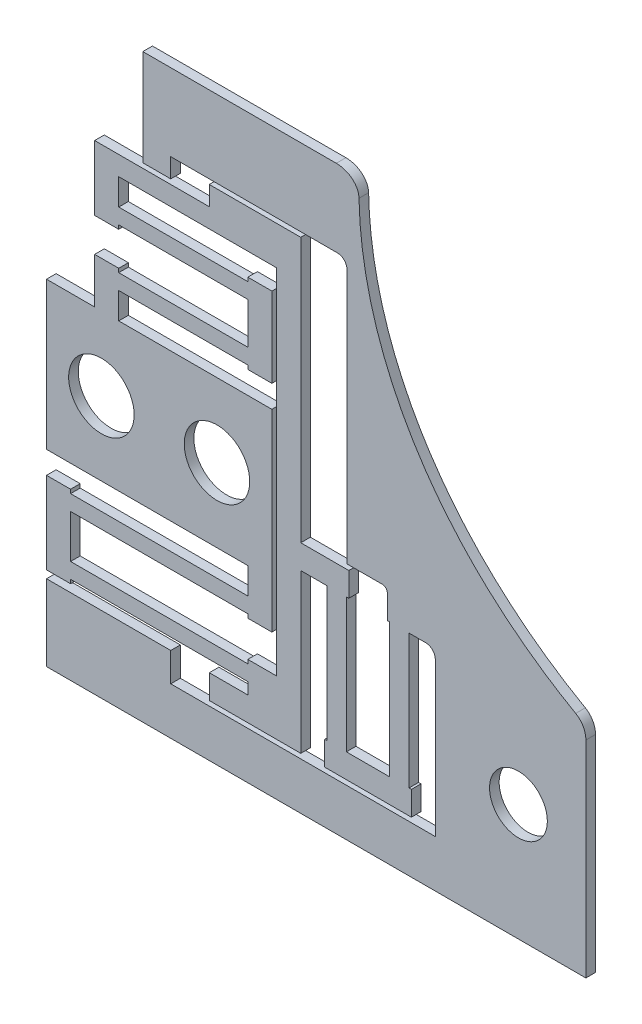
SolidWorks part; units mm, degrees
ref_plane "Front Plane" through (0, 0, 0) normal (0, 0, 1) x (1, 0, 0)
ref_plane "Top Plane" through (0, 0, 0) normal (0, 1, 0) x (1, 0, 0)
ref_plane "Right Plane" through (0, 0, 0) normal (1, 0, 0) x (0, 0, -1)
sketch "Sketch3" plane through (0, 0, 0) normal (0, 0, 1) x (1, 0, 0)
  line L80 (3.75, 14.9667) -> (11.7, 14.9667)
  line L81 (11.7, 14.9667) -> (11.7, 4.95)
  line L82 (0, 14.9667) -> (0, 7.3167)
  line L83 (0, 7.3167) -> (10.45, 7.3167)
  line L84 (1.25, 5.15) -> (1.25, 2.9)
  line L85 (1.25, 2.9) -> (10.45, 2.9)
  line L86 (10.45, 7.3167) -> (10.45, 5.95)
  line L87 (0, 6.15) -> (0, 1.9)
  line L88 (11.95, 21.45) -> (11.95, 3.1)
  line L89 (3.75, 16.3333) -> (10.45, 16.3333)
  line L90 (10.45, 17.1333) -> (10.45, 19.2833)
  line L91 (2.5, 19.0833) -> (2.5, 22.45)
  line L92 (3.75, 14.9667) -> (3.75, 16.3333)
  line L93 (11.7, 16.1333) -> (11.7, 20.2833)
  line L94 (3.75, 20.0833) -> (3.75, 21.45)
  line L95 (3.75, 21.45) -> (11.95, 21.45)
  line L96 (2.5, 22.45) -> (8.45, 22.45)
  line L97 (10.45, 16.3333) -> (10.45, 16.1333)
  line L98 (10.45, 16.1333) -> (11.7, 16.1333)
  line L99 (10.45, 17.1333) -> (3.75, 17.1333)
  line L100 (3.75, 17.1333) -> (3.75, 17.3333)
  line L101 (3.75, 17.3333) -> (2.5, 17.3333)
  line L102 (10.45, 19.2833) -> (3.75, 19.2833)
  line L103 (3.75, 19.2833) -> (3.75, 19.0833)
  line L104 (3.75, 19.0833) -> (2.5, 19.0833)
  line L105 (3.75, 20.0833) -> (10.45, 20.0833)
  line L106 (10.45, 20.0833) -> (10.45, 20.2833)
  line L107 (10.45, 20.2833) -> (11.7, 20.2833)
  line L108 (10.45, 5.95) -> (1.25, 5.95)
  line L109 (1.25, 5.95) -> (1.25, 6.15)
  line L110 (1.25, 6.15) -> (0, 6.15)
  line L111 (11.7, 4.95) -> (10.45, 4.95)
  line L112 (10.45, 4.95) -> (10.45, 5.15)
  line L113 (10.45, 5.15) -> (1.25, 5.15)
  line L114 (10.45, 2.9) -> (10.45, 3.1)
  line L115 (10.45, 3.1) -> (11.95, 3.1)
  line L116 (0, 1.9) -> (1.25, 1.9)
  line L117 (1.25, 1.9) -> (1.25, 2.1)
  line L118 (1.25, 2.1) -> (10.45, 2.1)
  line L119 (10.45, 2.1) -> (10.45, 1.5)
  line L120 (10.45, 1.5) -> (8.45, 1.5)
  line L121 (8.45, 1.5) -> (8.45, 0.25)
  line L122 (8.45, 0.25) -> (13.2, 0.25)
  line L123 (17.8167, 1.5) -> (15.5667, 1.5)
  line L124 (15.5667, 1.5) -> (15.5667, 8.4667)
  line L125 (15.5667, 8.4667) -> (15.6917, 8.4667)
  line L126 (17.8167, 8.4667) -> (17.8167, 1.5)
  line L127 (14.5667, 1.5) -> (14.4417, 1.5)
  line L128 (14.5667, 1.5) -> (14.5667, 8.4667)
  line L129 (14.5667, 8.4667) -> (13.2, 8.4667)
  line L130 (13.2, 9.7167) -> (15.6917, 9.7167)
  line L131 (19.6833, 8.4667) -> (18.8167, 8.4667)
  line L132 (18.8167, 8.4667) -> (18.8167, 1.5)
  line L133 (20.1833, 0) -> (20.1833, 7.9667)
  line L134 (20.1833, 0) -> (6.45, 0)
  line L135 (6.45, 0) -> (6.45, 1.5)
  line L136 (6.45, 1.5) -> (-4, 1.5)
  line L137 (-4, -2.45) -> (28, -2.45)
  line L138 (28, 27.7) -> (5, 27.7)
  line L139 (13.2, 0.25) -> (13.2, 8.4667)
  line L140 (6.45, 22.7) -> (5, 22.7)
  line L141 (5, 22.7) -> (5, 27.7)
  line L142 (18.9417, 1.5) -> (18.8167, 1.5)
  line L143 (17.4417, 9.9667) -> (15.6, 9.9667)
  line L144 (15.6, 9.9667) -> (15.6, 23.2)
  line L145 (14.4417, 1.5) -> (14.4417, 0.25)
  line L146 (18.9417, 1.5) -> (18.9417, 0.25)
  line L147 (18.9417, 0.25) -> (14.4417, 0.25)
  line L148 (13.2, 9.7167) -> (13.2, 23.45)
  line L149 (17.6917, 8.4667) -> (17.6917, 9.7167)
  line L150 (15.6917, 8.4667) -> (15.6917, 9.7167)
  line L151 (17.6917, 8.4667) -> (17.8167, 8.4667)
  line L152 (-4, -2.45) -> (-4, 1.5)
  line L153 (2.5, 14.9667) -> (0, 14.9667)
  line L154 (2.5, 14.9667) -> (2.5, 17.3333)
  line L155 (28, 27.7) -> (28, -2.45)
  line L156 (6.45, 22.7) -> (6.45, 23.7)
  line L157 (6.45, 23.7) -> (15.1, 23.7)
  line L158 (8.45, 22.45) -> (8.45, 23.45)
  line L159 (8.45, 23.45) -> (13.2, 23.45)
  line L160 (18.8167, 8.4667) -> (20.1833, 8.4667) construction
  line L161 (6.45, 0) -> (-4, 0) construction
  line L162 (0, 1.9) -> (0, -2.45) construction
  arc A8 (19.6833, 8.4667) -> (20.1833, 7.9667) centre (19.6833, 7.9667) cw
  arc A9 (17.6917, 9.7167) -> (17.4417, 9.9667) centre (17.4417, 9.7167) ccw
  arc A10 (15.1, 23.7) -> (15.6, 23.2) centre (15.1, 23.2) cw
  circle A11 centre (8.85, 11.1417) radius 1.7
  circle A12 centre (2.85, 11.1417) radius 1.7
  circle A13 centre (2.85, 11.1417) radius 2.85 construction
  circle A14 centre (8.85, 11.1417) radius 2.85 construction
  circle A15 centre (24.5, 3.6) radius 1.5
  point P93 (0, 11.1417)
  point P94 (3.125, 19.0833)
  point P96 (0, 0)
  dimension "D22" = 0.5
  dimension "D23" = 0.25
  dimension "D31" = 0.5
  dimension "D32" = 3.4
  dimension "D33" = 5.7
  dimension "D50" = 3.6
  dimension "D49" = 3
  dimension "D1" = 4.25
  dimension "D2" = 0.2
  dimension "D3" = 0.8
  dimension "D4" = 0.8
  dimension "D5" = 1.1667
  dimension "D6" = 0.8
  dimension "D7" = 1.75
  dimension "D8" = 0.8
  dimension "D9" = 1
  dimension "D10" = 0.25
  dimension "D11" = 1.25
  dimension "D12" = 0.25
  dimension "D13" = 1
  dimension "D14" = 7.65
  dimension "D15" = 1.25
  dimension "D16" = 1.25
  dimension "D17" = 0.25
  dimension "D18" = 1.25
  dimension "D19" = 2.4
  dimension "D20" = 0.25
  dimension "D21" = 5
  dimension "D24" = 5
  dimension "D25" = 1.25
  dimension "D26" = 2.5
  dimension "D27" = 2.5
  dimension "D28" = 2
  dimension "D29" = 0.25
  dimension "D30" = 1
  dimension "D34" = 6
  dimension "D35" = 4
  dimension "D36" = 32
  dimension "D37" = 1.1667
  dimension "D38" = 2
  dimension "D39" = 0.2
  dimension "D40" = 0.4
  dimension "D41" = 1.45
  dimension "D42" = 1
  dimension "D43" = 4.5
  dimension "D44" = 2
  dimension "D45" = 30.15
  dimension "D46" = 1.25
  dimension "D47" = 1.25
  dimension "D48" = 0.8667
  dimension "D51" = 3.5
extrude "Boss-Extrude2" add sketch "Sketch3" along normal blind 0.5
ref_plane "Plane2" through (0.2247, 0, 0.3596) normal (0.5299, 0, 0.848) x (0, -1, 0)
sketch "Sketch2" plane through (0.2247, 0, 0.3596) normal (0.5299, 0, 0.848) x (0, -1, 0)
  line L0 (0, 0) -> (0, 35.255) construction
  line L2 (0, 35.255) -> (-27.05, 35.255) construction
  circle A0 centre (-27.05, 35.255) radius 21.5
  dimension "D2" = 43
  dimension "D1" = 35.255
  dimension "D3" = 27.05
extrude "Cut-Extrude1" cut sketch "Sketch2" along normal through all
fillet "Fillet1" radius 1 2 edges at (28, 8.9751, 0.2506) (16.3874, 27.7, 0.25)
sketch "Sketch4" plane through (0, 0, 0) normal (0, 0, -1) x (-1, 0, 0)
  line L0 (-15.0436, 27.7) -> (-28, 27.7)
  line L1 (-28, 27.7) -> (-28, 8.2474)
  line L2 (4, 1.5) -> (0, 1.5)
  line L3 (-6.45, 1.5) -> (4, 1.5) construction
  line L4 (0, 1.5) -> (0, -2.45)
  line L5 (4, -2.45) -> (-28, -2.45) construction
  line L6 (0, -2.45) -> (4, -2.45)
  line L7 (4, -2.45) -> (4, 1.5)
  ellipse E0 centre (-41.5719, 27.05) end of major axis (-16.2196, 27.05) minor radius 21.5 (-27.4717, 9.1821) -> (-16.2227, 26.7156) ccw construction
  ellipse E2 centre (-15.0436, 26.7) end of major axis (-13.8645, 26.7) minor radius 1 (-15.0436, 27.7) -> (-16.2227, 26.7156) ccw construction
  spline S0 degree 3 poles (-16.2227, 26.7156) (-16.2445, 25.5077) (-16.4635, 23.6649) (-17.1502, 21.157) (-17.8905, 19.2872) (-18.9404, 17.2766) (-20.3354, 15.2064) (-22.0975, 13.212) (-24.4458, 11.1011) (-26.256, 9.872) (-27.4717, 9.1821) knots 0 0 0 0 0.166158 0.254199 0.357318 0.442333 0.566038 0.699963 0.807614 1 1 1 1
  spline S1 degree 3 poles (-16.2227, 26.7156) (-16.2204, 26.8898) (-16.1121, 27.1996) (-15.6875, 27.595) (-15.2923, 27.6998) (-15.0436, 27.7) knots 0 0 0 0 0.306492 0.558832 1 1 1 1
  spline S2 degree 3 poles (-27.4717, 9.1821) (-27.6349, 9.0901) (-27.9045, 8.81) (-28.0001, 8.4353) (-28, 8.2474) knots 0 0 0 0 0.499013 1 1 1 1
  spline S3 degree 3 poles (-27.4717, 9.1821) (-27.5539, 9.1354) (-27.6276, 9.0782) (-27.7588, 8.9443) (-27.8154, 8.8681) (-27.9518, 8.6234) (-28, 8.4364) (-28, 8.2474) knots 0 0 0 0 0.25 0.25 0.5 0.5 1 1 1 1 construction
extrude "Cut-Extrude2" cut sketch "Sketch4" against normal through all contours S2 S0 S1 L0 L1 | L7 L2 L4 L6 region at (23.1182, 20.3295, 0)
equation "\"FlexureNeckWidth\"= 0.2"
equation "\"FlexureGap\"=1.75"
equation "\"FlexureJointWidth\"=1.25"
equation "\"HorizontalFlexureWidth\"=1"
